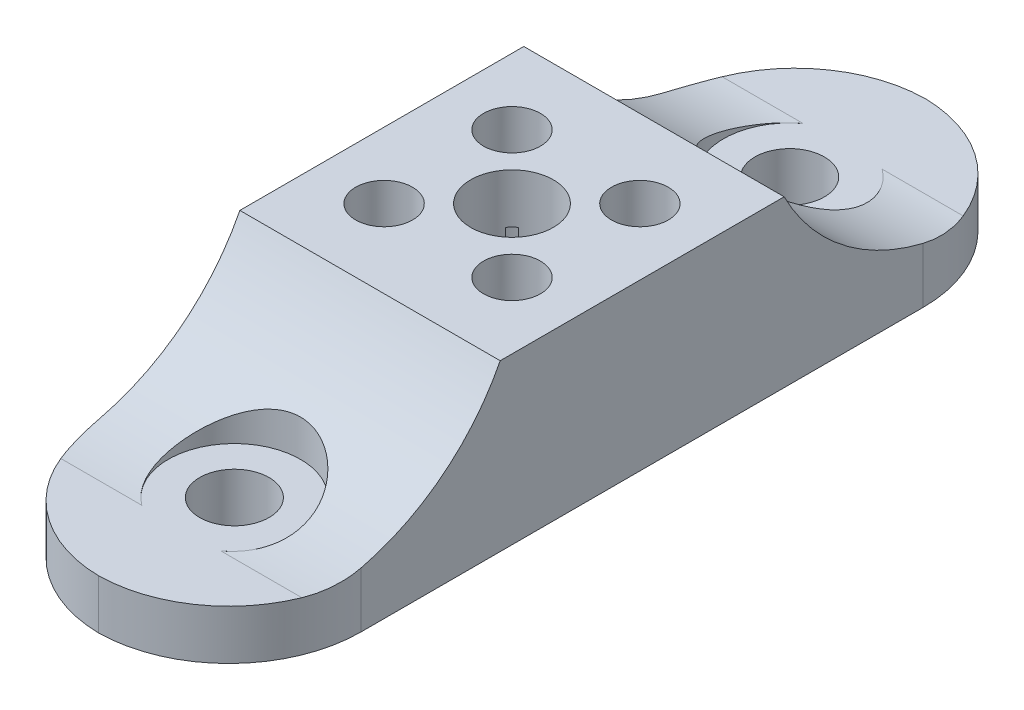
SolidWorks part; units mm, degrees
ref_plane "Front Plane" through (0, 0, 0) normal (0, 0, 1) x (1, 0, 0)
ref_plane "Top Plane" through (0, 0, 0) normal (0, 1, 0) x (1, 0, 0)
ref_plane "Right Plane" through (0, 0, 0) normal (1, 0, 0) x (0, 0, -1)
sketch "Sketch1" plane through (0, 0, 0) normal (0, 1, 0) x (1, 0, 0)
  line L1 (10, 31.75) -> (-10, 31.75)
  line L2 (10, 31.75) -> (10, -31.75)
  line L3 (10, -31.75) -> (-10, -31.75)
  line L4 (-10, 31.75) -> (-10, -31.75)
  line L5 (10, 31.75) -> (-10, -31.75) construction
  line L6 (10, -31.75) -> (-10, 31.75) construction
  point P0 (0, 0)
  dimension "D1" = 20
  dimension "D2" = 63.5
extrude "Boss-Extrude1" add sketch "Sketch1" along normal blind 12.7
sketch "Sketch2" plane through (0, 12.7, 0) normal (0, 1, 0) x (1, 0, 0)
  line L0 (0, 0) -> (0, -31.75) construction
  line L1 (-10, 0) -> (10, 0) construction
  line L2 (-10, 31.75) -> (-10, -31.75) construction
  line L3 (10, -31.75) -> (10, 31.75) construction
  line L4 (-4.9122, 4.9122) -> (4.9122, -4.9122) construction
  line L5 (-10, -31.75) -> (10, -31.75) construction
  line L6 (4.9122, 4.9122) -> (-4.9122, -4.9122) construction
  circle A0 centre (0, 0) radius 3.175
  circle A1 centre (-4.9122, 4.9122) radius 1.6764 construction
  circle A2 centre (4.9122, -4.9122) radius 1.6764 construction
  circle A3 centre (-4.9122, 4.9122) radius 2.1844
  circle A4 centre (4.9122, -4.9122) radius 2.1844
  circle A5 centre (-4.9122, -4.9122) radius 1.6764 construction
  circle A6 centre (4.9122, 4.9122) radius 1.6764 construction
  circle A7 centre (4.9122, 4.9122) radius 2.1844
  circle A8 centre (-4.9122, -4.9122) radius 2.1844
  point P1 (0, 0)
  point P4 (0, 0)
  point P19 (0, -13.6572)
  point P21 (0, -31.75)
  dimension "D2" = 6.35
  dimension "D3" = 3.3528
  dimension "D4" = 10.541
  dimension "D1" = 45
  dimension "D5" = 0.508
extrude "Cut-Extrude1" cut sketch "Sketch2" against normal through all
sketch "Sketch3" plane through (0, 0, 0) normal (1, 0, 0) x (0, 0, -1)
  line L0 (31.75, 3.81) -> (-31.75, 3.81) construction
  line L1 (31.75, 12.7) -> (31.75, 0) construction
  line L2 (-31.75, 12.7) -> (-31.75, 0) construction
  line L3 (31.75, 0) -> (-31.75, 0) construction
  line L4 (31.75, 12.7) -> (-31.75, 12.7) construction
  line L6 (31.75, 12.7) -> (31.75, 0)
  line L7 (31.75, 12.7) -> (-31.75, 12.7)
  line L8 (0, 12.7) -> (0, 0) construction
  line L9 (31.75, 3.81) -> (25.4, 3.81)
  line L10 (7.0966, 0) -> (7.0966, 12.7) construction
  line L11 (-31.75, 3.81) -> (-25.4, 3.81)
  line L12 (-31.75, 12.7) -> (-31.75, 0)
  arc A0 (25.4, 3.81) -> (10.9066, 12.7) centre (25.4, 20.0693) cw
  arc A1 (-25.4, 3.81) -> (-10.9066, 12.7) centre (-25.4, 20.0693) ccw
  dimension "D1" = 3.81
  dimension "D2" = 3.81
  dimension "D3" = 6.35
extrude "Cut-Extrude2" cut sketch "Sketch3" against normal through all both and the other way through all contours A0 L9 L6 L7 | L11 A1 L7 L12 region at (0, 8.7446, 23.0689) region at (0, 8.7446, -23.0689)
sketch "Sketch4" plane through (0, 0, 0) normal (0, -1, 0) x (1, 0, 0)
  line L0 (0, 31.75) -> (0, -31.75) construction
  line L1 (-10, 31.75) -> (10, 31.75) construction
  line L2 (10, -31.75) -> (-10, -31.75) construction
  circle A0 centre (0, 0) radius 5.334
  circle A1 centre (-4.9122, -4.9122) radius 3.81
  circle A2 centre (4.9122, 4.9122) radius 3.81
  circle A3 centre (-4.9122, 4.9122) radius 3.81
  circle A4 centre (4.9122, -4.9122) radius 3.81
  circle M3 centre (-4.9122, -4.9122) radius 2.1844
  circle M4 centre (4.9122, 4.9122) radius 2.1844
  circle M5 centre (0, 0) radius 3.175
  circle M13 centre (-4.9122, 4.9122) radius 2.1844
  circle M14 centre (4.9122, -4.9122) radius 2.1844
  dimension "D1" = 10.668
  dimension "D2" = 7.62
extrude "Cut-Extrude3" cut sketch "Sketch4" against normal blind 8.89 contours A0 A1 M3 | A0 A1 M3 | A0 M3 | A0 A2 M4 | A0 M4 | A0 A2 M4 | A3 A0 M13 M5 | A3 A0 M13 | A4 A0 M14 M5 | A4 A0 M14 region at (2.952, 0, 2.952) region at (5.0602, 0, 2.0014) region at (7.6327, 0, -2.4009) region at (2.952, 0, -2.952) region at (3.5867, 0, 3.5867) region at (-2.952, 0, 2.952) region at (-2.0014, 0, 5.0602) region at (-7.5302, 0, -7.5302) region at (-2.952, 0, -2.952) region at (-3.5867, 0, -3.5867)
extrude "Cut-Extrude4" cut sketch "Sketch4<3>" against normal blind 3.81 contours A3 A0 M13 M5 | A0 M13 | A3 A0 A1 M5 | A0 A1 M5 M3 | A0 M3 | L0 A0 A4 M5 | L0 A1 A0 M5 | A4 A0 M14 M5 | A0 M14 | A4 A0 A2 M5 | A0 A2 M5 M4 | A0 M4 | L0 A0 A3 M5 | A0 L0 A2 M5 | L0 A4 A2 M5 | L0 A3 A1 M5 region at (0.6716, 0, 4.0685) region at (-0.6716, 0, 4.0685) region at (1.3454, 0, 0) region at (-1.3454, 0, 0) region at (2.952, 0, 2.952) region at (-2.952, 0, 2.952) region at (0.6716, 0, -4.0685) region at (-0.6716, 0, -4.0685) region at (3.5867, 0, 3.5867) region at (-3.5867, 0, 3.5867) region at (-4.0685, 0, 0) region at (-2.952, 0, -2.952) region at (2.952, 0, -2.952) region at (4.0685, 0, 0) region at (-3.5867, 0, -3.5867) region at (3.5867, 0, -3.5867)
sketch "Sketch4<3>" plane through (0, 0, 0) normal (0, -1, 0) x (1, 0, 0) same geometry as "Sketch4"
sketch "Sketch6" plane through (0, 3.81, 0) normal (0, 1, 0) x (1, 0, 0)
  line L0 (0, 31.75) -> (0, 10.9066) construction
  line L1 (-10, 31.75) -> (10, 31.75) construction
  line L2 (-10, 10.9066) -> (10, 10.9066) construction
  line L3 (10, 0) -> (-10, 0) construction
  line L4 (10, -10.9066) -> (10, 10.9066) construction
  line L5 (-10, 10.9066) -> (-10, -10.9066) construction
  line L6 (0, -31.75) -> (0, -10.9066) construction
  circle A0 centre (0, 21.3283) radius 2.667
  circle A1 centre (0, 21.3283) radius 5.08
  circle A2 centre (0, -21.3283) radius 5.08
  circle A3 centre (0, -21.3283) radius 2.667
  dimension "D1" = 5.334
  dimension "D2" = 10.16
extrude "Cut-Extrude5" cut sketch "Sketch6" along normal up to surface (8.89 mm away) contours A2 A3 | A3 | A1 region at (-4.9363, 3.81, 21.3283) region at (0, 3.81, 21.3283) up to face at (0, 12.7, 3.175)
extrude "Cut-Extrude6" cut sketch "Sketch6<4>" against normal through all contours A0 | A3 region at (0, 3.81, -21.3283) region at (0, 3.81, 21.3283)
sketch "Sketch6<4>" plane through (0, 3.81, 0) normal (0, 1, 0) x (1, 0, 0) same geometry as "Sketch6"
fillet "Fillet1" radius 10.16 4 edges at (10, 1.905, 31.75) (10, 1.905, -31.75) (-10, 1.905, 31.75) (-10, 1.905, -31.75)
